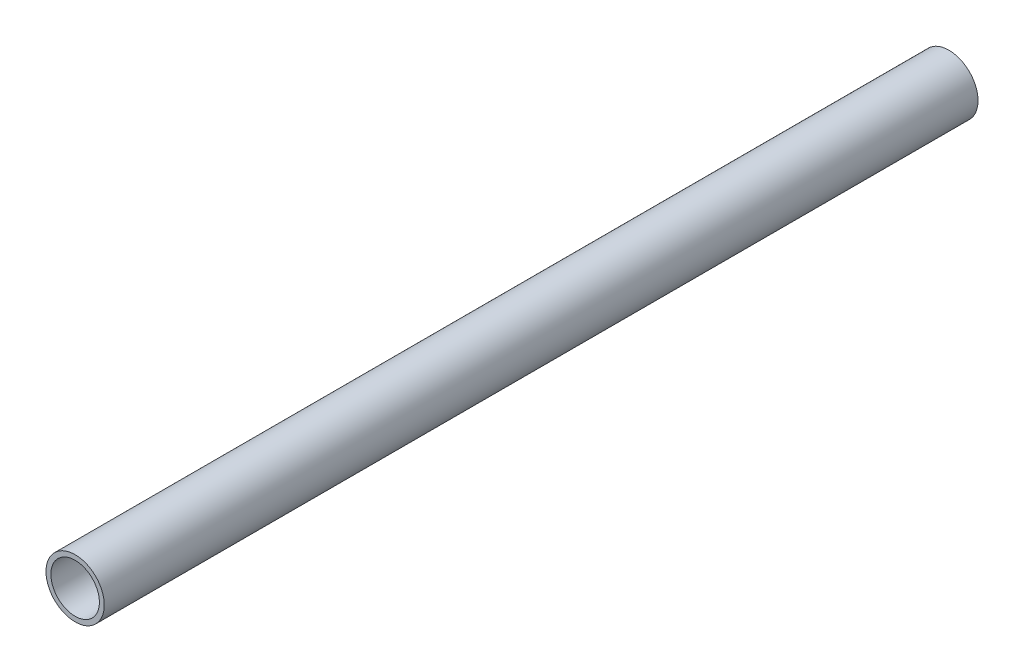
SolidWorks part; units mm, degrees
ref_plane "Front Plane" through (0, 0, 0) normal (0, 0, 1) x (1, 0, 0)
ref_plane "Top Plane" through (0, 0, 0) normal (0, 1, 0) x (1, 0, 0)
ref_plane "Right Plane" through (0, 0, 0) normal (1, 0, 0) x (0, 0, -1)
sketch "Sketch1" plane through (0, 0, 0) normal (0, 0, 1) x (1, 0, 0)
  circle A0 centre (0, 0) radius 6
  circle A1 centre (0, 0) radius 5
  dimension "D1" = 12
  dimension "D2" = 10
extrude "Boss-Extrude1" add sketch "Sketch1" along normal blind 180
